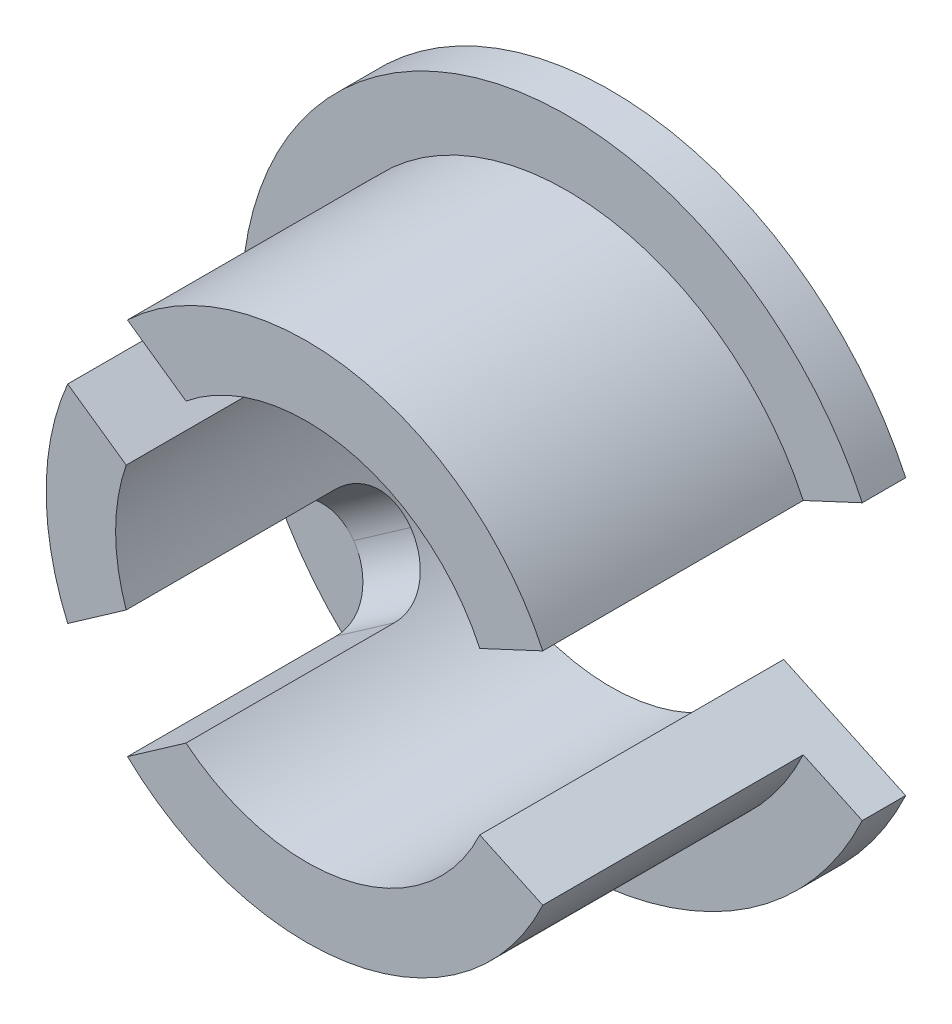
SolidWorks part; units mm, degrees
ref_plane "Front Plane" through (0, 0, 0) normal (0, 0, 1) x (1, 0, 0)
ref_plane "Top Plane" through (0, 0, 0) normal (0, 1, 0) x (1, 0, 0)
ref_plane "Right Plane" through (0, 0, 0) normal (1, 0, 0) x (0, 0, -1)
sketch "Sketch1" plane through (0, 0, 0) normal (0, 0, 1) x (1, 0, 0)
  line L0 (3.9878, 1.8595) -> (5.4378, 2.5357)
  line L1 (5.4378, -2.5357) -> (3.9878, -1.8595)
  line L2 (-3.9, 0) -> (-4.4, 0) construction
  line L3 (-6, 0) -> (-6.5, 0) construction
  circle A0 centre (0, 0) radius 3.9 construction
  arc A1 (0, 6.5) -> (0, -6.5) centre (0, 0) ccw construction
  arc A2 (5.4378, 2.5357) -> (5.4378, -2.5357) centre (0, 0) ccw
  arc A3 (3.9878, -1.8595) -> (3.9878, 1.8595) centre (0, 0) cw
  dimension "D1" = 7.8
  dimension "D2" = 6.5
  dimension "D3" = 1.6
  dimension "D4" = 50
extrude "Boss-Extrude1" add sketch "Sketch1" along normal blind 6
sketch "Sketch2" plane through (0, 0, 0) normal (0, 0, -1) x (-1, 0, 0)
  line L0 (-3.9878, 1.8595) -> (-5.4378, 2.5357) construction
  line L1 (-3.9878, 1.8595) -> (-5.4378, 2.5357)
  line L2 (-5.4378, -2.5357) -> (-3.9878, -1.8595) construction
  line L3 (-5.4378, -2.5357) -> (-3.9878, -1.8595)
  line L4 (-5.4378, 2.5357) -> (-6.7973, 3.1696)
  line L5 (-5.4378, -2.5357) -> (-6.7973, -3.1696)
  circle A0 centre (0, 0) radius 7.5
  circle A1 centre (0, 0) radius 4.4
  arc M1 (-5.4378, -2.5357) -> (-5.4378, 2.5357) centre (0, 0) ccw
  line M2 (-5.4378, 2.5357) -> (-3.9878, 1.8595)
  arc M3 (-3.9878, 1.8595) -> (-3.9878, -1.8595) centre (0, 0) cw
  line M4 (-3.9878, -1.8595) -> (-5.4378, -2.5357)
  dimension "D1" = 15
  dimension "D2" = 8.8
extrude "Boss-Extrude2" add sketch "Sketch2" along normal blind 1 contours M4 M1 M2 M3 | L5 A0 L4 M1 region at (4.6427, 2.3479, 0) region at (6.03, 3.0405, 0)
sketch "Sketch3" plane through (0, 0, 6) normal (0, 0, 1) x (1, 0, 0)
  line L0 (0, 0) -> (-14.0798, 0) construction
  line L1 (-5.3762, -5.2294) -> (-2.7793, -3.411)
  line L2 (-6.7528, -3.2634) -> (-4.1559, -1.4451)
  line L3 (0, 0) -> (-11.4084, -7.9882) construction
  line L4 (-4.0778, -4.3202) -> (-5.4544, -2.3543) construction
  line L5 (0, 0) -> (-11.4084, 7.9882) construction
  line L6 (-4.0778, 4.3202) -> (-5.4544, 2.3543) construction
  line L7 (-6.7528, 3.2634) -> (-4.1559, 1.4451)
  line L8 (-5.3762, 5.2294) -> (-2.7793, 3.411)
  arc A0 (6.7973, 3.1696) -> (6.7973, -3.1696) centre (0, 0) ccw construction
  arc A1 (3.9878, 1.8595) -> (3.9878, -1.8595) centre (0, 0) ccw construction
  arc A2 (6.7973, 3.1696) -> (6.7973, -3.1696) centre (0, 0) ccw
  arc A3 (3.9878, 1.8595) -> (3.9878, -1.8595) centre (0, 0) ccw
  arc M7 (5.4378, 2.5357) -> (5.4378, -2.5357) centre (0, 0) ccw
  arc M9 (3.9878, -1.8595) -> (3.9878, 1.8595) centre (0, 0) cw
  dimension "D1" = 2.4
  dimension "D2" = 70
extrude "Cut-Extrude1" cut sketch "Sketch3" against normal blind 6 contours L2 L1 M7 M9 | L8 A2 L7 M7 | L8 L7 M7 M9 | L2 A2 L1 M7 region at (-5.4995, -3.8508, 6) region at (-4.2202, -2.955, 6) region at (-5.4995, 3.8508, 6) region at (-4.2202, 2.955, 6)
fillet "Fillet1" radius 1.2 4 edges at (-3.4533, -3.883, 0) (-4.8299, -1.917, 0) (-3.4533, 3.883, 0) (-4.8299, 1.917, 0)
